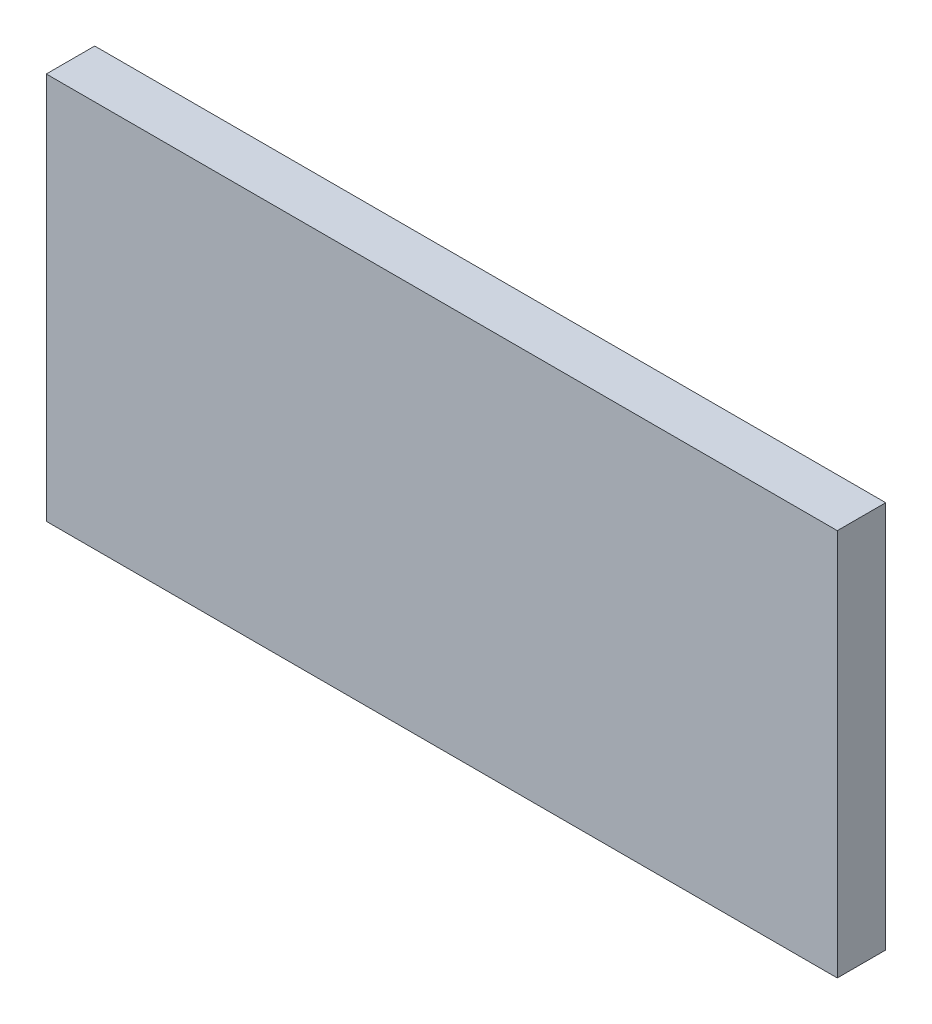
SolidWorks part; units mm, degrees
ref_plane "Front Plane" through (0, 0, 0) normal (0, 0, 1) x (1, 0, 0)
ref_plane "Top Plane" through (0, 0, 0) normal (0, 1, 0) x (1, 0, 0)
ref_plane "Right Plane" through (0, 0, 0) normal (1, 0, 0) x (0, 0, -1)
sketch "Sketch1" plane through (0, 0, 0) normal (0, 0, 1) x (1, 0, 0)
  line L1 (98, -48) -> (-98, -48)
  line L2 (98, -48) -> (98, 48)
  line L3 (98, 48) -> (-98, 48)
  line L4 (-98, -48) -> (-98, 48)
  line L5 (98, -48) -> (-98, 48) construction
  line L6 (98, 48) -> (-98, -48) construction
  point P0 (0, 0)
extrude "Extrude1" add sketch "Sketch1" against normal blind 12
